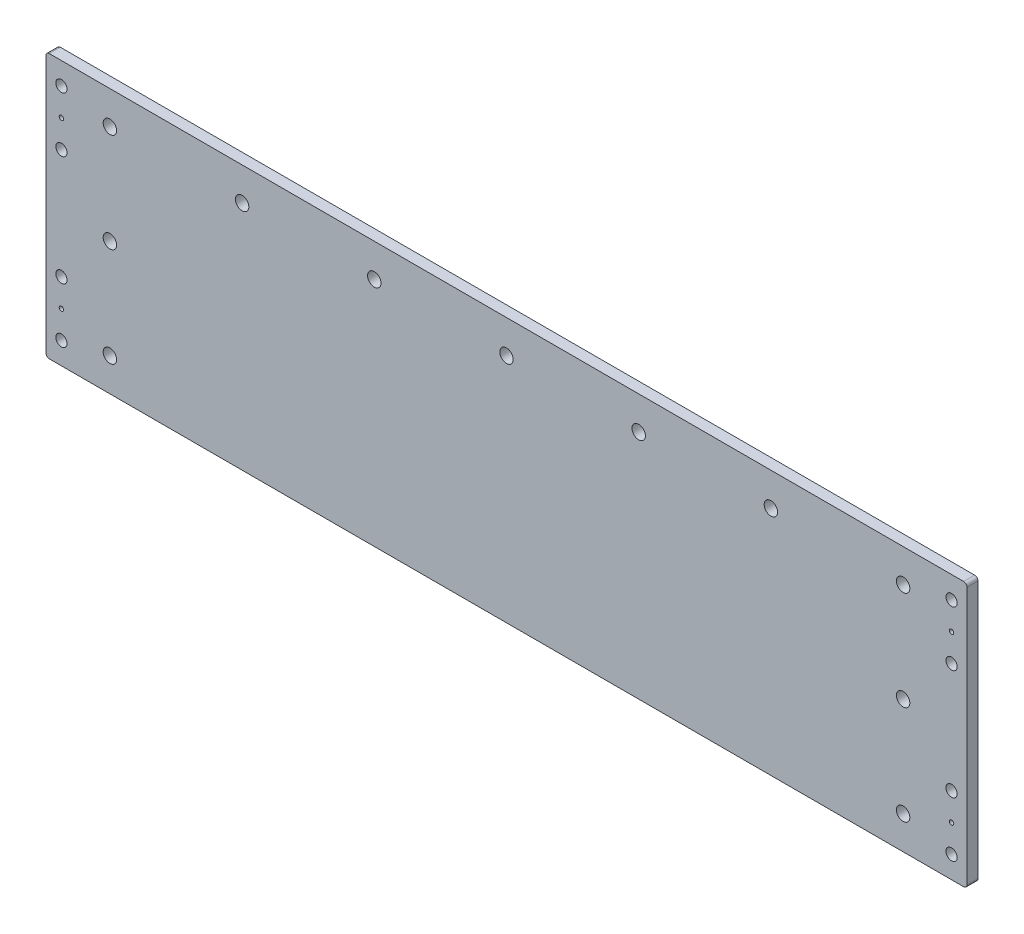
SolidWorks part; units mm, degrees
ref_plane "Front Plane" through (0, 0, 0) normal (0, 0, 1) x (1, 0, 0)
ref_plane "Top Plane" through (0, 0, 0) normal (0, 1, 0) x (1, 0, 0)
ref_plane "Right Plane" through (0, 0, 0) normal (1, 0, 0) x (0, 0, -1)
sketch "Sketch1" plane through (0, 0, 0) normal (0, 0, 1) x (1, 0, 0)
  line L1 (209, -60) -> (-209, -60)
  line L2 (209, -60) -> (209, 60)
  line L3 (209, 60) -> (-209, 60)
  line L4 (-209, -60) -> (-209, 60)
  line L5 (209, -60) -> (-209, 60) construction
  line L6 (209, 60) -> (-209, -60) construction
  point P0 (0, 0)
  dimension "D1" = 418
  dimension "D2" = 120
extrude "Boss-Extrude1" add sketch "Sketch1" along normal mid plane 5
sketch "Sketch3" plane through (0, 0, 2.5) normal (0, 0, 1) x (1, 0, 0)
  line L0 (-209, 45) -> (209, 45) construction
  line L1 (-209, 60) -> (-209, -60) construction
  line L2 (209, -60) -> (209, 60) construction
  line L3 (-209, -45) -> (209, -45) construction
  line L4 (-180, 60) -> (-180, -60) construction
  line L5 (209, 60) -> (-209, 60) construction
  line L6 (-209, -60) -> (209, -60) construction
  line L7 (180, 60) -> (180, -60) construction
  line L8 (-120, 60) -> (-120, -60) construction
  line L9 (120, 60) -> (120, -60) construction
  line L10 (-1000, 0) -> (49000, 0) construction
  circle A0 centre (-180, 45) radius 3.05
  circle A1 centre (180, 45) radius 3.05
  circle A2 centre (180, -45) radius 3.05
  circle A3 centre (-180, -45) radius 3.05
  circle A4 centre (0, 45) radius 3.05
  circle A5 centre (-120, 45) radius 3.05
  circle A6 centre (120, 45) radius 3.05
  circle A7 centre (-180, 0) radius 3.05
  circle A8 centre (-60, 45) radius 3.05
  circle A9 centre (60, 45) radius 3.05
  circle A10 centre (180, 0) radius 3.05
  dimension "D5" = 6.1
  dimension "D6" = 6.1
  dimension "D7" = 6.1
  dimension "D8" = 6.1
  dimension "D9" = 6.1
  dimension "D12" = 6.1
  dimension "D13" = 6.1
  dimension "D14" = 6.1
  dimension "D11" = 6.1
  dimension "D15" = 6.1
  dimension "D19" = 6.1
  dimension "D1" = 29
  dimension "D2" = 15
  dimension "D3" = 29
  dimension "D4" = 15
  dimension "D10" = 60
  dimension "D16" = 60
  dimension "D17" = 60
  dimension "D18" = 60
extrude "Cut-Extrude2" cut sketch "Sketch3" against normal through all
fillet "Fillet1" radius 1.5 4 edges at (-209, -60, 0) (209, -60, 0) (209, 60, 0) (-209, 60, 0)
sketch "Sketch4" plane through (0, 0, 2.5) normal (0, 0, 1) x (1, 0, 0)
  line L0 (-202, -1005.069) -> (-202, 48994.931) construction
  line L1 (-209, 58.5) -> (-209, -58.5) construction
  line L2 (207.5, 60) -> (-207.5, 60) construction
  circle A0 centre (-202, 50) radius 2.55
  circle A1 centre (-202, 37.5) radius 1
  circle A2 centre (-202, 25) radius 2.55
  dimension "D2" = 5.1
  dimension "D6" = 5.1
  dimension "D7" = 2
  dimension "D1" = 7
  dimension "D3" = 10
  dimension "D4" = 22.5
  dimension "D5" = 35
extrude "Cut-Extrude3" cut sketch "Sketch4" against normal through all
mirror "Mirror1" about plane through (0, 0, 0) normal (0, 1, 0) of "Cut-Extrude3"
mirror "Mirror2" about plane through (0, 0, 0) normal (1, 0, 0) of "Mirror1", "Cut-Extrude3"
equation "\"D6@Sketch3\"=6.1"
equation "\"D13@Sketch3\"=\"D6@Sketch3\""
equation "\"D9@Sketch3\"=\"D6@Sketch3\""
equation "\"D12@Sketch3\"=\"D6@Sketch3\""
equation "\"D7@Sketch3\"=\"D6@Sketch3\""
equation "\"D5@Sketch3\"=\"D6@Sketch3\""
equation "\"D8@Sketch3\"=\"D6@Sketch3\""
equation "\"D14@Sketch3\"=\"D6@Sketch3\""
equation "\"D1@Sketch3\"=15+14"
equation "\"D3@Sketch3\"=15+14"
equation "\"D11@Sketch3\"=\"D6@Sketch3\""
equation "\"D19@Sketch3\"=\"D6@Sketch3\""
